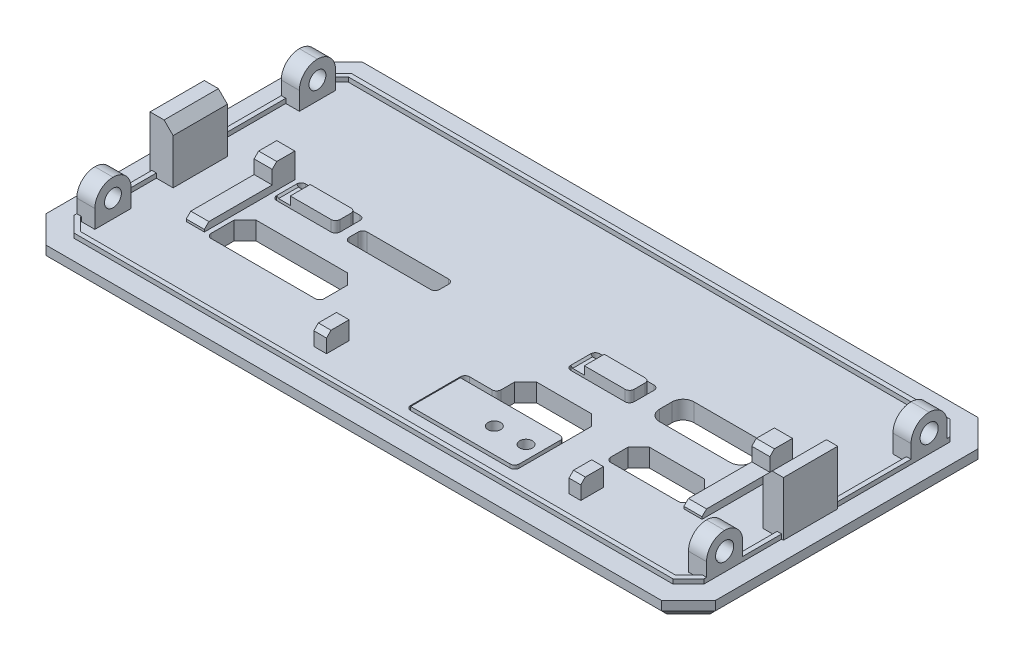
SolidWorks part; units mm, degrees
ref_plane "前视基准面" through (0, 0, 0) normal (0, 0, 1) x (1, 0, 0)
ref_plane "上视基准面" through (0, 0, 0) normal (0, 1, 0) x (1, 0, 0)
ref_plane "右视基准面" through (0, 0, 0) normal (1, 0, 0) x (0, 0, -1)
other "Configuration Table"
sketch "草图2" plane through (0, 0, 0) normal (0, 1, 0) x (1, 0, 0)
  line L0 (-36.7624, 30.764) -> (-33.7624, 33.764)
  line L1 (-36.7624, 1.764) -> (-33.7624, -1.236)
  line L2 (-33.7624, 33.764) -> (34.2376, 33.764)
  line L3 (-36.7624, 30.764) -> (-36.7624, 1.764)
  line L4 (-33.7624, -1.236) -> (34.2376, -1.236)
  line L5 (37.2376, 30.764) -> (37.2376, 1.764)
  line L6 (34.2376, -1.236) -> (37.2376, 1.764)
  line L7 (34.2376, 33.764) -> (37.2376, 30.764)
  point P5 (-36.7624, -1.236)
  point P7 (-36.7624, -1.236)
  point P8 (37.2376, 33.764)
  point P10 (37.2376, 33.764)
  point P11 (37.2376, -1.236)
  point P13 (-36.7624, 33.764)
  point P15 (-36.7624, 33.764)
  dimension "D1" = 74
  dimension "D2" = 35
extrude "凸台-拉伸1" add sketch "草图2" along normal blind 2
chamfer "倒角1" distance 1 angle 45 8 edges at (-36.7624, 0, -16.264) (0.2376, 0, -33.764) (0.2376, 0, 1.236) (37.2376, 0, -16.264) (-35.2624, 0, -32.264) (-35.2624, 0, -0.264) (35.7376, 0, -0.264) (35.7376, 0, -32.264)
sketch "草图3" plane through (0, 0, 0) normal (0, -1, 0) x (1, 0, 0)
  line L1 (-25.7624, -8.514) -> (-13.2624, -8.514)
  line L2 (-25.7624, -8.514) -> (-25.7624, -12.764)
  line L3 (-25.7624, -12.764) -> (-13.2624, -12.764)
  line L4 (-13.2624, -8.514) -> (-13.2624, -12.764)
  line L5 (1.7376, -3.064) -> (13.7376, -3.064)
  line L7 (5.2376, -12.764) -> (13.7376, -12.764)
  line L8 (13.7376, -3.064) -> (13.7376, -12.764)
  line L9 (17.7376, -9.164) -> (26.2376, -9.164)
  line L10 (17.7376, -9.164) -> (17.7376, -12.764)
  line L11 (17.7376, -12.764) -> (26.2376, -12.764)
  line L12 (26.2376, -9.164) -> (26.2376, -12.764)
  line L13 (15.8376, -15.764) -> (26.0376, -15.764)
  line L14 (15.8376, -15.764) -> (15.8376, -19.564)
  line L15 (15.8376, -19.564) -> (26.0376, -19.564)
  line L16 (26.0376, -15.764) -> (26.0376, -19.564)
  line L17 (6.7376, -15.764) -> (13.7376, -15.764)
  line L18 (6.7376, -15.764) -> (6.7376, -18.964)
  line L19 (6.7376, -18.964) -> (13.7376, -18.964)
  line L20 (13.7376, -15.764) -> (13.7376, -18.964)
  line L21 (-25.7624, -15.764) -> (-18.7624, -15.764)
  line L22 (-25.7624, -15.764) -> (-25.7624, -18.964)
  line L23 (-25.7624, -18.964) -> (-18.7624, -18.964)
  line L24 (-18.7624, -15.764) -> (-18.7624, -18.964)
  line L25 (-17.7624, -15.764) -> (-7.7624, -15.764)
  line L26 (-17.7624, -15.764) -> (-17.7624, -17.764)
  line L27 (-17.7624, -17.764) -> (-7.7624, -17.764)
  line L28 (-7.7624, -15.764) -> (-7.7624, -17.764)
  line L29 (-36.7624, -30.764) -> (-36.7624, -1.764) construction
  line L30 (-34.7624, -15.764) -> (-43.2418, -15.764) construction
  line L31 (37.2376, -1.764) -> (37.2376, -30.764) construction
  line L32 (-35.2588, -12.764) -> (-41.1207, -12.764) construction
  line L33 (-33.7624, 1.236) -> (34.2376, 1.236) construction
  line L34 (34.2376, -33.764) -> (-33.7624, -33.764) construction
  line L35 (5.2376, -12.764) -> (5.2376, -9.564)
  line L36 (5.2376, -9.564) -> (1.7376, -9.564)
  line L37 (1.7376, -9.564) -> (1.7376, -3.064)
  dimension "D1" = 14
  dimension "D2" = 18
  dimension "D3" = 12.5
  dimension "D4" = 4.25
  dimension "D5" = 3.2
  dimension "D6" = 2
  dimension "D7" = 7
  dimension "D8" = 11
  dimension "D9" = 1
  dimension "D10" = 10
  dimension "D11" = 23.5
  dimension "D12" = 7
  dimension "D13" = 3.8
  dimension "D14" = 3.6
  dimension "D15" = 11
  dimension "D16" = 11.2
  dimension "D17" = 10.2
  dimension "D18" = 8.5
  dimension "D19" = 12
  dimension "D20" = 6.5
  dimension "D21" = 8.5
  dimension "D22" = 3.2
  dimension "D23" = 29
extrude "切除-拉伸1" cut sketch "草图3" against normal up to next
fillet "圆角1" radius 1.2 4 edges at (26.0376, 1, -15.764) (26.0376, 1, -19.564) (15.8376, 1, -19.564) (15.8376, 1, -15.764)
fillet "圆角2" radius 0.5 20 edges at (-7.7624, 1, -15.764) (-7.7624, 1, -17.764) (-17.7624, 1, -17.764) (-17.7624, 1, -15.764) (-18.7624, 1, -18.964) (-18.7624, 1, -15.764) (-25.7624, 1, -18.964) (-25.7624, 1, -15.764) (6.7376, 1, -18.964) (13.7376, 1, -18.964) (13.7376, 1, -15.764) (6.7376, 1, -15.764) (13.7376, 1, -3.064) (17.7376, 1, -9.164) (26.2376, 1, -9.164) (-13.2624, 1, -8.514) (-25.7624, 1, -8.514) (1.7376, 1, -3.064) (1.7376, 1, -9.564) (5.2376, 1, -9.564)
chamfer "倒角2" distance 1.2 angle 45 6 edges at (26.2376, 1, -12.764) (17.7376, 1, -12.764) (13.7376, 1, -12.764) (-13.2624, 1, -12.764) (-25.7624, 1, -12.764) (5.2376, 1, -12.764)
sketch "草图4" plane through (0, 0, 0) normal (0, -1, 0) x (1, 0, 0)
  line L0 (13.2376, -3.064) -> (2.2376, -3.064) construction
  line L1 (-22.7624, -16.264) -> (-19.2624, -16.264)
  line L2 (-22.7624, -16.264) -> (-22.7624, -18.464)
  line L3 (-22.7624, -18.464) -> (-19.2624, -18.464)
  line L4 (-19.2624, -16.264) -> (-19.2624, -18.464)
  line L5 (6.7376, -3.564) -> (13.2376, -3.564)
  line L6 (6.7376, -3.564) -> (6.7376, -9.064)
  line L7 (6.7376, -9.064) -> (13.2376, -9.064)
  line L8 (13.2376, -3.564) -> (13.2376, -9.064)
  line L9 (8.7376, -16.264) -> (13.2376, -16.264)
  line L10 (8.7376, -16.264) -> (8.7376, -18.464)
  line L11 (8.7376, -18.464) -> (13.2376, -18.464)
  line L12 (13.2376, -16.264) -> (13.2376, -18.464)
  line L13 (13.7376, -11.564) -> (13.7376, -3.564) construction
  line L15 (2.2376, -9.564) -> (4.7376, -9.564) construction
  line L16 (13.7376, -18.464) -> (13.7376, -16.264) construction
  line L17 (7.2376, -18.964) -> (13.2376, -18.964) construction
  line L18 (13.2376, -15.764) -> (7.2376, -15.764) construction
  line L19 (-19.2624, -15.764) -> (-25.2624, -15.764) construction
  line L20 (-25.2624, -18.964) -> (-19.2624, -18.964) construction
  line L21 (-18.7624, -18.464) -> (-18.7624, -16.264) construction
  dimension "D1" = 0.5
  dimension "D2" = 6.5
  dimension "0.5" = 0.5
  dimension "D3" = 0.5
  dimension "D4" = 0.5
  dimension "D5" = 0.5
  dimension "D6" = 0.5
  dimension "D7" = 4.5
  dimension "D8" = 0.5
  dimension "D9" = 0.5
  dimension "D10" = 0.5
  dimension "D11" = 3.5
extrude "凸台-拉伸2" add sketch "草图4" against normal blind 1 separate body
sketch "草图5" plane through (0, 1, 0) normal (0, 1, 0) x (1, 0, 0)
  line L0 (-25.7624, 18.464) -> (-25.7624, 16.264) construction
  line L1 (-19.2624, 16.264) -> (-25.7624, 16.264)
  line L2 (-19.2624, 16.264) -> (-19.2624, 18.464)
  line L3 (-19.2624, 18.464) -> (-25.7624, 18.464)
  line L4 (-25.7624, 16.264) -> (-25.7624, 18.464)
  line L5 (8.7376, 18.464) -> (13.2376, 18.464) construction
  line L6 (13.2376, 16.264) -> (6.7376, 16.264)
  line L7 (13.2376, 16.264) -> (13.2376, 18.464)
  line L8 (13.2376, 18.464) -> (6.7376, 18.464)
  line L9 (6.7376, 16.264) -> (6.7376, 18.464)
extrude "凸台-拉伸3" add sketch "草图5" along normal blind 0.8
sketch "草图16" plane through (0, 1.8, 0) normal (0, 1, 0) x (1, 0, 0)
  line L0 (13.2376, 18.464) -> (6.7376, 18.464) construction
  line L1 (13.2376, 16.264) -> (8.2376, 16.264)
  line L2 (13.2376, 16.264) -> (13.2376, 18.464)
  line L3 (13.2376, 18.464) -> (8.2376, 18.464)
  line L4 (8.2376, 16.264) -> (8.2376, 18.464)
  line L5 (-25.7624, 16.264) -> (-19.2624, 16.264) construction
  line L6 (-19.2624, 18.464) -> (-24.2624, 18.464)
  line L7 (-19.2624, 18.464) -> (-19.2624, 16.264)
  line L8 (-19.2624, 16.264) -> (-24.2624, 16.264)
  line L9 (-24.2624, 18.464) -> (-24.2624, 16.264)
  dimension "D1" = 5
extrude "凸台-拉伸10" add sketch "草图16" along normal blind 0.9
sketch "草图6" plane through (0, 1, 0) normal (0, 1, 0) x (1, 0, 0)
  line L2 (13.2376, 3.564) -> (1.7376, 3.564)
  line L3 (13.2376, 3.564) -> (13.2376, 9.064)
  line L4 (13.2376, 9.064) -> (1.7376, 9.064)
  line L5 (1.7376, 3.564) -> (1.7376, 9.064)
extrude "凸台-拉伸4" add sketch "草图6" along normal blind 0.9
fillet "圆角5" radius 1 3 edges at (6.7376, 1, -17.364) (-25.7624, 1, -17.364) (1.7376, 1, -6.314)
fillet "圆角3" radius 0.5 12 edges at (8.7376, 0.5, -16.264) (8.7376, 0.5, -18.464) (13.2376, 1.35, -18.464) (13.2376, 1.35, -16.264) (-19.2624, 1.35, -16.264) (-19.2624, 1.35, -18.464) (-22.7624, 0.5, -18.464) (-22.7624, 0.5, -16.264) (13.2376, 0.95, -3.564) (6.7376, 0.5, -3.564) (13.2376, 0.95, -9.064) (6.7376, 0.5, -9.064)
chamfer "倒角3" distance 0.2 angle 45 2 edges at (-25.7624, 1.8, -17.364) (6.7376, 1.8, -17.364)
sketch "草图7" plane through (0, 2, 0) normal (0, 1, 0) x (1, 0, 0)
  line L0 (34.2376, -1.236) -> (-33.7624, -1.236) construction
  line L1 (-7.8624, 6.364) -> (-9.2624, 6.364)
  line L2 (-7.8624, 6.364) -> (-7.8624, 3.864)
  line L3 (-7.8624, 3.864) -> (-9.2624, 3.864)
  line L4 (-9.2624, 6.364) -> (-9.2624, 3.864)
  line L5 (20.2376, 3.864) -> (18.9376, 3.864)
  line L6 (20.2376, 3.864) -> (20.2376, 6.364)
  line L7 (20.2376, 6.364) -> (18.9376, 6.364)
  line L8 (18.9376, 3.864) -> (18.9376, 6.364)
  line L9 (37.2376, 1.764) -> (37.2376, 30.764) construction
  line L10 (-36.7624, 1.764) -> (-36.7624, 30.764) construction
  dimension "D1" = 5.1
  dimension "D2" = 17
  dimension "D3" = 27.5
  dimension "D4" = 1.3
  dimension "D5" = 1.4
  dimension "D6" = 2.5
extrude "凸台-拉伸5" add sketch "草图7" along normal blind 2
sketch "草图11" plane through (0, 2, 0) normal (0, 1, 0) x (1, 0, 0)
  line L0 (-33.7624, -1.236) -> (34.2376, -1.236) construction
  line L1 (28.7376, 8.764) -> (26.7376, 8.764)
  line L2 (28.7376, 8.764) -> (28.7376, 18.764)
  line L3 (28.7376, 18.764) -> (26.7376, 18.764)
  line L4 (26.7376, 8.764) -> (26.7376, 18.764)
  line L5 (-26.2624, 8.764) -> (-28.2624, 8.764)
  line L6 (-26.2624, 8.764) -> (-26.2624, 18.764)
  line L7 (-26.2624, 18.764) -> (-28.2624, 18.764)
  line L8 (-28.2624, 8.764) -> (-28.2624, 18.764)
  line L9 (-36.7624, 30.764) -> (-36.7624, 1.764) construction
  line L10 (37.2376, 1.764) -> (37.2376, 30.764) construction
  dimension "D1" = 10
  dimension "D2" = 8.5
  dimension "D3" = 2
  dimension "D4" = 10
  dimension "D5" = 8.5
  dimension "D6" = 2
extrude "凸台-拉伸7" add sketch "草图11" along normal blind 0.75
sketch "草图12" plane through (0, 2.75, 0) normal (0, 1, 0) x (1, 0, 0)
  line L0 (26.7376, 18.764) -> (26.7376, 8.764) construction
  line L1 (28.7376, 18.764) -> (26.7376, 18.764)
  line L2 (28.7376, 18.764) -> (28.7376, 16.264)
  line L3 (28.7376, 16.264) -> (26.7376, 16.264)
  line L4 (26.7376, 18.764) -> (26.7376, 16.264)
  line L5 (-28.2624, 18.764) -> (-28.2624, 8.764) construction
  line L6 (-26.2624, 18.764) -> (-28.2624, 18.764)
  line L7 (-26.2624, 18.764) -> (-26.2624, 16.264)
  line L8 (-26.2624, 16.264) -> (-28.2624, 16.264)
  line L9 (-28.2624, 18.764) -> (-28.2624, 16.264)
  dimension "D1" = 2.5
extrude "凸台-拉伸8" add sketch "草图12" along normal blind 2
chamfer "倒角4" distance 0.5 angle 45 6 edges at (-8.5624, 4, -3.864) (19.5876, 4, -3.864) (-27.2624, 2.75, -8.764) (27.7376, 2.75, -8.764) (-27.2624, 4.75, -16.264) (27.7376, 4.75, -16.264)
sketch "草图8" plane through (0, 2, 0) normal (0, 1, 0) x (1, 0, 0)
  line L1 (35.0376, 2.964) -> (33.0376, 2.964)
  line L2 (35.0376, 2.964) -> (35.0376, 6.964)
  line L3 (35.0376, 6.964) -> (33.0376, 6.964)
  line L4 (33.0376, 2.964) -> (33.0376, 6.964)
  line L6 (35.0376, 25.564) -> (33.0376, 25.564)
  line L7 (35.0376, 25.564) -> (35.0376, 29.564)
  line L8 (35.0376, 29.564) -> (33.0376, 29.564)
  line L9 (33.0376, 25.564) -> (33.0376, 29.564)
  line L10 (-34.5624, 2.964) -> (-32.5624, 2.964)
  line L11 (-34.5624, 2.964) -> (-34.5624, 6.964)
  line L12 (-34.5624, 6.964) -> (-32.5624, 6.964)
  line L13 (-32.5624, 2.964) -> (-32.5624, 6.964)
  line L15 (-34.5624, 25.564) -> (-32.5624, 25.564)
  line L16 (-34.5624, 25.564) -> (-34.5624, 29.564)
  line L17 (-34.5624, 29.564) -> (-32.5624, 29.564)
  line L18 (-32.5624, 25.564) -> (-32.5624, 29.564)
  line L21 (-36.7624, 30.764) -> (-36.7624, 1.764) construction
  line L22 (34.2376, 33.764) -> (-33.7624, 33.764) construction
  line L23 (-33.7624, -1.236) -> (34.2376, -1.236) construction
  line L24 (37.2376, 1.764) -> (37.2376, 30.764) construction
  dimension "D1" = 4
  dimension "D2" = 2.2
  dimension "D3" = 4.2
  dimension "D4" = 4.2
  dimension "D5" = 2.2
  dimension "D6" = 2
extrude "凸台-拉伸6" add sketch "草图8" along normal blind 4
fillet "圆角4" radius 2 8 edges at (34.0376, 6, -6.964) (34.0376, 6, -2.964) (34.0376, 6, -29.564) (34.0376, 6, -25.564) (-33.5624, 6, -25.564) (-33.5624, 6, -29.564) (-33.5624, 6, -2.964) (-33.5624, 6, -6.964)
sketch "草图9" plane through (-34.5624, 0, 0) normal (-1, 0, 0) x (0, 0, 1)
  circle A0 centre (-4.964, 4) radius 1
  circle A1 centre (-27.564, 4) radius 1
  dimension "D1" = 2
extrude "切除-拉伸2" cut sketch "草图9" against normal up to next (2 mm away) draft 2
sketch "草图10" plane through (35.0376, 0, 0) normal (1, 0, 0) x (0, 0, -1)
  circle A0 centre (4.964, 4) radius 1
  circle A1 centre (27.564, 4) radius 1
  dimension "D1" = 2
extrude "切除-拉伸3" cut sketch "草图10" against normal up to next (2 mm away) draft 2
sketch "草图13" plane through (0, 2, 0) normal (0, 1, 0) x (1, 0, 0)
  line L0 (35.2376, 29.9355) -> (35.2376, 2.5924) construction
  line L1 (35.2376, 11.264) -> (32.9876, 11.264)
  line L2 (35.2376, 11.264) -> (35.2376, 17.264)
  line L3 (35.2376, 17.264) -> (32.9876, 17.264)
  line L4 (32.9876, 11.264) -> (32.9876, 17.264)
  line L5 (-34.7624, 2.5924) -> (-34.7624, 29.9355) construction
  line L6 (-34.7624, 11.264) -> (-32.2124, 11.264)
  line L7 (-34.7624, 11.264) -> (-34.7624, 17.264)
  line L8 (-34.7624, 17.264) -> (-32.2124, 17.264)
  line L9 (-32.2124, 11.264) -> (-32.2124, 17.264)
  line L10 (34.2376, -1.236) -> (-33.7624, -1.236) construction
  dimension "D1" = 12.5
  dimension "D2" = 6
  dimension "D3" = 2.25
  dimension "D4" = 2.55
extrude "凸台-拉伸9" add sketch "草图13" along normal blind 6
chamfer "倒角5" distance 1 angle 45 2 edges at (-32.2124, 8, -14.264) (32.9876, 8, -14.264)
sketch "草图14" plane through (0, 0, 0) normal (0, -1, 0) x (1, 0, 0)
  line L0 (7.0755, -6.314) -> (5.3752, -6.314) construction
  line L3 (13.2376, -8.564) -> (13.2376, -4.064) construction
  circle A0 centre (11.7376, -6.314) radius 0.7
  circle A1 centre (8.2376, -6.314) radius 0.7
  point P5 (13.2376, -6.314)
  dimension "D1" = 1.4
  dimension "D2" = 3.5
  dimension "D3" = 1.5
extrude "切除-拉伸4" cut sketch "草图14" against normal up to next
sketch "草图17" plane through (0, 2, 0) normal (0, 1, 0) x (1, 0, 0)
  line L8 (33.1192, 31.064) -> (-32.644, 31.064)
  line L9 (-32.644, 31.064) -> (-34.0624, 29.6456)
  line L10 (-34.0624, 29.6456) -> (-34.0624, 2.8823)
  line L11 (-34.0624, 2.8823) -> (-32.644, 1.464)
  line L12 (-32.644, 1.464) -> (33.1192, 1.464)
  line L13 (33.1192, 1.464) -> (34.5376, 2.8823)
  line L14 (34.5376, 2.8823) -> (34.5376, 29.6456)
  line L15 (34.5376, 29.6456) -> (33.1192, 31.064)
  line L16 (33.3264, 31.564) -> (-32.8511, 31.564)
  line L17 (-32.8511, 31.564) -> (-34.5624, 29.8527)
  line L18 (-34.5624, 29.8527) -> (-34.5624, 2.6752)
  line L19 (-34.5624, 2.6752) -> (-32.8511, 0.964)
  line L20 (-32.8511, 0.964) -> (33.3264, 0.964)
  line L21 (33.3264, 0.964) -> (35.0376, 2.6752)
  line L22 (35.0376, 2.6752) -> (35.0376, 29.8527)
  line L23 (35.0376, 29.8527) -> (33.3264, 31.564)
  line L24 (33.3264, 31.564) -> (-32.8511, 31.564)
  line L25 (-32.8511, 31.564) -> (-34.5624, 29.8527)
  line L26 (-34.5624, 29.8527) -> (-34.5624, 2.6752)
  line L27 (-34.5624, 2.6752) -> (-32.8511, 0.964)
  line L28 (-32.8511, 0.964) -> (33.3264, 0.964)
  line L29 (33.3264, 0.964) -> (35.0376, 2.6752)
  line L30 (35.0376, 2.6752) -> (35.0376, 29.8527)
  line L31 (35.0376, 29.8527) -> (33.3264, 31.564)
  dimension "D1" = 2.2
  dimension "D2" = 0.5
extrude "凸台-拉伸11" add sketch "草图17" along normal blind 0.5
